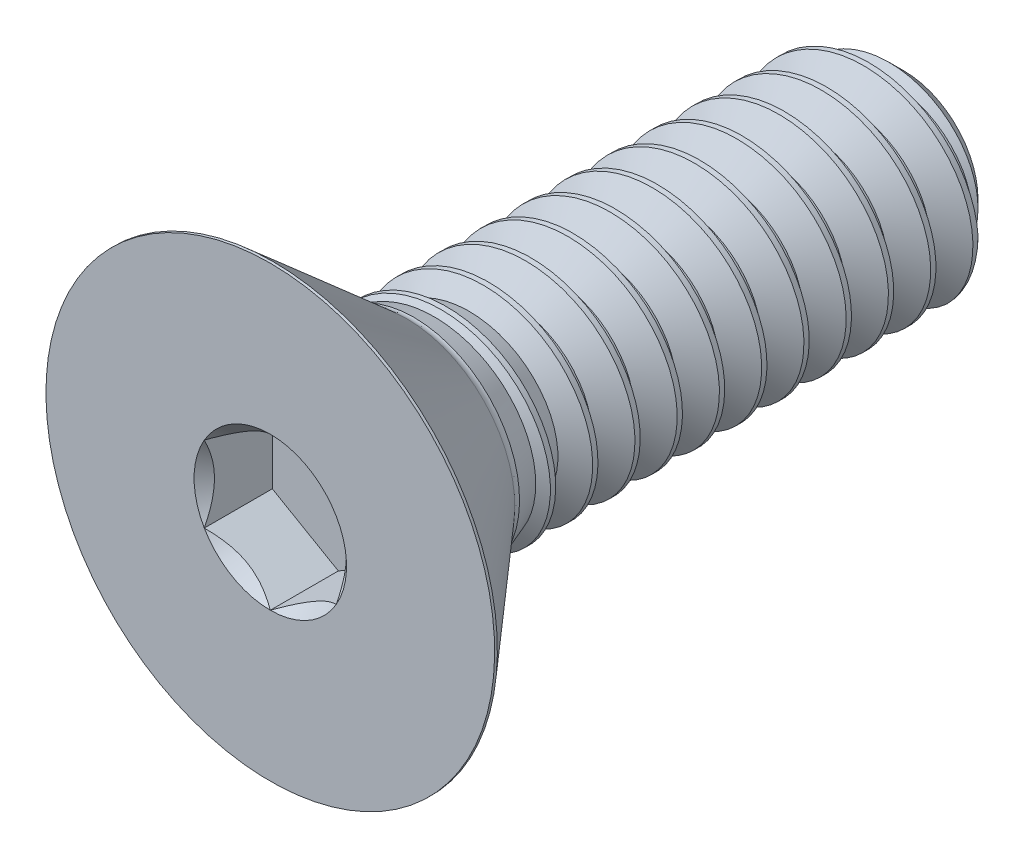
SolidWorks part; units mm, degrees
ref_plane "Front Plane" through (0, 0, 0) normal (0, 0, 1) x (1, 0, 0)
ref_plane "Top Plane" through (0, 0, 0) normal (0, 1, 0) x (1, 0, 0)
ref_plane "Right Plane" through (0, 0, 0) normal (1, 0, 0) x (0, 0, -1)
sketch "Sketch1" plane through (0, 0, 0) normal (1, 0, 0) x (0, 0, -1)
  line L0 (-9.525, 0) -> (9.525, 0) construction
  line L1 (-9.525, 0) -> (-9.525, 6.7437)
  line L2 (-9.525, 6.7437) -> (-9.4432, 6.7437)
  line L3 (-9.4432, 6.7437) -> (-5.4356, 3.2599)
  line L4 (-9.4432, -6.7437) -> (-5.4356, -3.2599)
  line L5 (9.525, 0) -> (9.525, 3.175)
  line L6 (9.525, 3.175) -> (-5.4356, 3.175)
  line L7 (8.5725, 3.175) -> (9.525, 2.2225)
  line L8 (9.4456, 3.3125) -> (10.0806, 2.2126) construction
  line L9 (10.0806, 2.2126) -> (10.7156, 3.3125) construction
  line L10 (10.7156, 3.3125) -> (9.4456, 3.3125) construction
  line L11 (9.4853, 3.2437) -> (10.6759, 3.2437)
  line L12 (10.6759, 3.2437) -> (10.16, 2.3501)
  line L13 (10.16, 2.3501) -> (10.0012, 2.3501)
  line L14 (10.0012, 2.3501) -> (9.4853, 3.2437)
  line L15 (10.0806, 2.3501) -> (10.0806, 2.2126) construction
  line L16 (9.525, 3.175) -> (10.6362, 3.175) construction
  line L17 (10.0806, 3.3125) -> (10.0806, 3.175) construction
  line L18 (9.525, -3.175) -> (-5.4356, -3.175)
  arc A0 (-5.4356, 3.2599) -> (-5.2084, 3.175) centre (-5.2084, 3.5213) ccw
  point P2 (0, 0)
  point P23 (-7.4803, 0)
  point P27 (10.0806, 3.2437)
  point P30 (7.62, -3.175)
  point P34 (-9.4432, -6.7437)
  dimension "Length" = 19.05
  dimension "Head Height" = 4.0894
  dimension "Head Diameter" = 13.4874
  dimension "Countersink Angle" = 82
  dimension "Thread Diameter" = 6.35
  dimension "D2" = 0.0818
  dimension "Pitch" = 1.27
  dimension "D4" = 0.1588
  dimension "D3" = 45
  dimension "D5" = 0.9525
  dimension "D6" = 2.0447
  dimension "D1" = 1.905
sketch "Sketch2" plane through (0, 0, 0) normal (0, 0, 1) x (1, 0, 0)
  line L1 (0, 2.2914) -> (-1.9844, 1.1457)
  line L2 (-1.9844, 1.1457) -> (-1.9844, -1.1457)
  line L3 (-1.9844, -1.1457) -> (0, -2.2914)
  line L4 (0, -2.2914) -> (1.9844, -1.1457)
  line L5 (1.9844, -1.1457) -> (1.9844, 1.1457)
  line L6 (1.9844, 1.1457) -> (0, 2.2914)
  circle A0 centre (0, 0) radius 1.9844 construction
  dimension "Drive Size" = 3.9688
sketch "Sketch11" plane through (0, 0, 0) normal (1, 0, 0) x (0, 0, -1)
  line L0 (-9.4432, 6.7437) -> (-5.4356, 3.2599) construction
  line L1 (-9.525, 0) -> (-9.525, 6.7437) construction
  line L2 (-9.4432, 6.7437) -> (-5.4356, 3.2599)
  line L3 (-9.525, 0) -> (-9.525, 6.7437)
  line L4 (-9.525, 6.7437) -> (-9.4432, 6.7437) construction
  line L5 (-9.525, 6.7437) -> (-9.4432, 6.7437)
  line L6 (-5.2084, 3.175) -> (8.5725, 3.175)
  line L7 (8.5725, 3.175) -> (9.525, 2.2225)
  line L8 (9.525, 2.2225) -> (9.525, 0)
  line L9 (9.525, 0) -> (-9.525, 0)
  arc A0 (-5.4356, 3.2599) -> (-5.2084, 3.175) centre (-5.2084, 3.5213) ccw construction
  arc A1 (-5.4356, 3.2599) -> (-5.2084, 3.175) centre (-5.2084, 3.5213) ccw
revolve "Revolve1" add sketch "Sketch11" angle 360 about L9
sketch "Sketch9" plane through (0, 0, 9.525) normal (0, 0, 1) x (1, 0, 0)
  line L0 (1.9844, -1.1457) -> (1.9844, 1.1457) construction
  line L1 (0, -2.2914) -> (1.9844, -1.1457) construction
  line L2 (-1.9844, -1.1457) -> (0, -2.2914) construction
  line L3 (-1.9844, 1.1457) -> (-1.9844, -1.1457) construction
  line L4 (0, 2.2914) -> (-1.9844, 1.1457) construction
  line L5 (1.9844, 1.1457) -> (0, 2.2914) construction
  line L6 (1.9844, -1.1457) -> (1.9844, 1.1457)
  line L7 (0, -2.2914) -> (1.9844, -1.1457)
  line L8 (-1.9844, -1.1457) -> (0, -2.2914)
  line L9 (-1.9844, 1.1457) -> (-1.9844, -1.1457)
  line L10 (0, 2.2914) -> (-1.9844, 1.1457)
  line L11 (1.9844, 1.1457) -> (0, 2.2914)
sketch "Sketch10" plane through (0, 0, 9.525) normal (0, 0, 1) x (1, 0, 0)
  circle A0 centre (0, 0) radius 2.2914
extrude "Cut-Extrude2" cut sketch "Sketch10" against normal up to vertex (2.0447 mm away) draft 45 up to point (0, 0, 7.4803)
extrude "Cut-Extrude1" cut sketch "Sketch9" against normal up to vertex (2.0447 mm away) up to point (0, 0, 7.4803)
ref_plane "Plane1" through (0, 0, 5.2084) normal (0, 0, 1) x (1, 0, 0)
split "Split1" trim tools "Plane1" bodies to split 111 resulting bodies 105 106
sketch "Sketch3" plane through (0, 0, -9.525) normal (0, 0, -1) x (-1, 0, 0)
  circle A0 centre (0, 0) radius 3.175 construction
  circle A1 centre (0, 0) radius 3.175
curve "Helix/Spiral1" pitch 1.27 height 19.05 turns 15
sketch "Sketch4" plane through (0, 0, 0) normal (1, 0, 0) x (0, 0, -1)
  line L0 (9.4853, 3.2437) -> (10.6759, 3.2437) construction
  line L1 (10.0012, 2.3501) -> (9.4853, 3.2437) construction
  line L2 (10.16, 2.3501) -> (10.0012, 2.3501) construction
  line L3 (10.6759, 3.2437) -> (10.16, 2.3501) construction
  line L4 (9.4853, 3.2437) -> (10.6759, 3.2437)
  line L5 (10.0012, 2.3501) -> (9.4853, 3.2437)
  line L6 (10.16, 2.3501) -> (10.0012, 2.3501)
  line L7 (10.6759, 3.2437) -> (10.16, 2.3501)
sweep "Cut-Sweep1" cut profiles "Sketch4" path "Helix/Spiral1" align with end faces yes
sketch "Sketch7" plane through (0, 0, 5.2084) normal (0, 0, 1) x (1, 0, 0)
  circle A0 centre (0, 0) radius 3.175
extrude "Boss-Extrude2" add sketch "Sketch7" against normal up to next (14.7334 mm away) draft 20
equation "\"D2@Sketch1\"=\"Head Height@Sketch1\"/50"
equation "\"D4@Sketch1\" = \"Pitch@Sketch1\" / 8"
equation "\"D5@Sketch1\"=\"Pitch@Sketch1\"*0.75"
equation "\"D4@Helix/Spiral1\"=\"Pitch@Sketch1\""
equation "\"D3@Helix/Spiral1\"=\"Length@Sketch1\""
equation "\"D6@Sketch1\"=\"Head Height@Sketch1\"/2"
equation "\"D1@Sketch1\"=\"Pitch@Sketch1\"*1.5"
